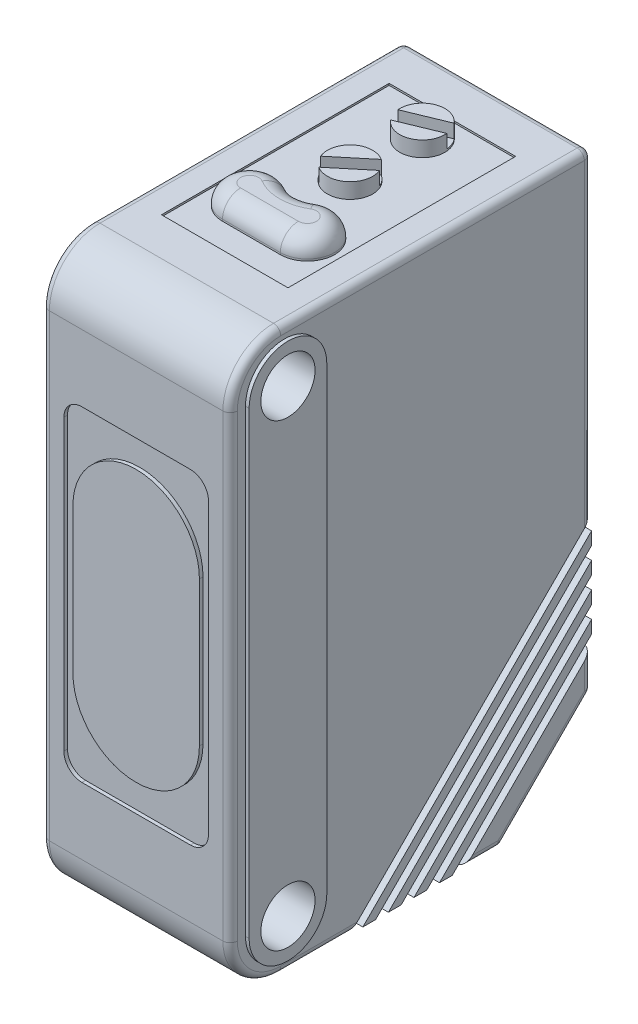
SolidWorks part; units mm, degrees
ref_plane "Plan de face" through (0, 0, 0) normal (0, 0, 1) x (1, 0, 0)
ref_plane "Plan de dessus" through (0, 0, 0) normal (0, 1, 0) x (1, 0, 0)
ref_plane "Plan de droite" through (0, 0, 0) normal (1, 0, 0) x (0, 0, -1)
sketch "Esquisse1" plane through (0, 0, 0) normal (1, 0, 0) x (0, 0, -1)
  line L0 (3, 28.2) -> (3, 2.8) construction
  line L1 (2.8, 0) -> (15, 0)
  line L2 (0, 2.8) -> (0, 28.2)
  line L3 (2.8, 31) -> (20, 31)
  line L4 (20, 5) -> (20, 31)
  line L5 (20, 5) -> (15, 0)
  circle A0 centre (3, 28.2) radius 1.5
  circle A1 centre (3, 2.8) radius 1.5
  arc A2 (2.8, 0) -> (0, 2.8) centre (2.8, 2.8) cw
  arc A3 (0, 28.2) -> (2.8, 31) centre (2.8, 28.2) cw
  point P11 (0, 0)
  dimension "D4" = 3
  dimension "D5" = 3
  dimension "D8" = 2.8
  dimension "D1" = 20
  dimension "D2" = 31
  dimension "D3" = 17
  dimension "D6" = 25.4
  dimension "D7" = 2.8
  dimension "D9" = 5
  dimension "D10" = 45
extrude "Boss.-Extru.1" add sketch "Esquisse1" along normal blind 10.4
sketch "Esquisse2" plane through (10.4, 0, 0) normal (1, 0, 0) x (0, 0, -1)
  line L0 (3, 28.2) -> (3, 2.8) construction
  line L1 (5.15, 28.2) -> (5.15, 2.8)
  line L2 (0.85, 28.2) -> (0.85, 2.8)
  arc A0 (5.15, 28.2) -> (0.85, 28.2) centre (3, 28.2) ccw
  arc A1 (0.85, 2.8) -> (5.15, 2.8) centre (3, 2.8) ccw
  circle A2 centre (3, 28.2) radius 1.5 construction
  circle A3 centre (3, 28.2) radius 1.5
  circle A4 centre (3, 2.8) radius 1.5
  point P3 (3, 15.5)
  dimension "D1" = 2.15
extrude "Boss.-Extru.3" add sketch "Esquisse2" along normal blind 0.2
sketch "Esquisse3" plane through (0, 0, 0) normal (-1, 0, 0) x (0, 0, 1)
  line L0 (-3, 28.2) -> (-3, 2.8) construction
  line L1 (-0.85, 28.2) -> (-0.85, 2.8)
  line L2 (-5.15, 28.2) -> (-5.15, 2.8)
  arc A0 (-0.85, 28.2) -> (-5.15, 28.2) centre (-3, 28.2) ccw
  arc A1 (-5.15, 2.8) -> (-0.85, 2.8) centre (-3, 2.8) ccw
  circle A2 centre (-3, 2.8) radius 1.5
  circle A3 centre (-3, 28.2) radius 1.5
  point P4 (-3, 15.5)
extrude "Boss.-Extru.4" add sketch "Esquisse3" along normal blind 0.2
sketch "Esquisse4" plane through (0, 0, 0) normal (0, 0, 1) x (1, 0, 0)
  line L0 (1.2, 15.5) -> (9.2, 15.5) construction
  line L1 (2.2, 24.5) -> (8.2, 24.5)
  line L2 (1.2, 23.5) -> (1.2, 7.5)
  line L3 (2.2, 6.5) -> (8.2, 6.5)
  line L4 (9.2, 23.5) -> (9.2, 7.5)
  line L5 (5.2, 24.5) -> (5.2, 6.5) construction
  line L6 (10.4, 0) -> (0, 0) construction
  line L7 (8.7, 19.5) -> (8.7, 11.5)
  line L8 (1.7, 19.5) -> (1.7, 11.5)
  line L9 (10.4, 28.2) -> (10.4, 2.8) construction
  arc A0 (8.7, 19.5) -> (1.7, 19.5) centre (5.2, 19.5) ccw
  arc A1 (1.7, 11.5) -> (8.7, 11.5) centre (5.2, 11.5) ccw
  arc A2 (1.2, 7.5) -> (2.2, 6.5) centre (2.2, 7.5) ccw
  arc A3 (8.2, 6.5) -> (9.2, 7.5) centre (8.2, 7.5) ccw
  arc A4 (8.2, 24.5) -> (9.2, 23.5) centre (8.2, 23.5) cw
  arc A5 (2.2, 24.5) -> (1.2, 23.5) centre (2.2, 23.5) ccw
  dimension "D2" = 4
  dimension "D5" = 8
  dimension "D7" = 1
  dimension "D1" = 18
  dimension "D3" = 4
  dimension "D4" = 15.5
  dimension "D6" = 5.2
extrude "Enlèv. mat.-Extru.1" cut sketch "Esquisse4" against normal blind 0.2
sketch "Esquisse5" plane through (10.4, 0, 0) normal (1, 0, 0) x (0, 0, -1)
  line L0 (13, 0) -> (20, 7)
  line L1 (2.8, 0) -> (15, 0) construction
  line L2 (20, 5) -> (20, 31) construction
  line L3 (20, 7) -> (20, 7.7071)
  line L4 (20, 7.7071) -> (12.2929, 0)
  line L5 (12.2929, 0) -> (13, 0)
  line L6 (11.5858, 0) -> (20, 8.4142)
  line L7 (20, 8.4142) -> (20, 9.1213)
  line L8 (20, 9.1213) -> (10.8787, 0)
  line L9 (10.8787, 0) -> (11.5858, 0)
  line L10 (20, 9.8284) -> (10.1716, 0)
  line L11 (10.1716, 0) -> (9.4645, 0)
  line L12 (9.4645, 0) -> (20, 10.5355)
  line L13 (20, 10.5355) -> (20, 9.8284)
  line L14 (20, 11.2426) -> (8.7574, 0)
  line L15 (8.7574, 0) -> (8.0503, 0)
  line L16 (8.0503, 0) -> (20, 11.9497)
  line L17 (20, 11.9497) -> (20, 11.2426)
  line L18 (7.3431, 0) -> (20, 12.6569)
  line L19 (20, 12.6569) -> (20, 13.364)
  line L20 (20, 13.364) -> (6.636, 0)
  line L21 (6.636, 0) -> (7.3431, 0)
  dimension "D1" = 2
  dimension "D2" = 45
  dimension "D3" = 0.5
  dimension "D4" = 0.5
  dimension "D5" = 0.5
  dimension "D6" = 0.5
  dimension "D7" = 0.5
  dimension "D8" = 0.5
  dimension "D9" = 0.5
  dimension "D10" = 0.5
  dimension "D11" = 0.5
extrude "Enlèv. mat.-Extru.3" cut sketch "Esquisse5" against normal blind 0.5
sketch "Esquisse7" plane through (0, 0, 0) normal (-1, 0, 0) x (0, 0, 1)
  line L0 (-20, 7) -> (-13, 0)
  line L1 (-20, 5) -> (-20, 31) construction
  line L2 (-2.8, 0) -> (-15, 0) construction
  line L3 (-13, 0) -> (-12.2929, 0)
  line L4 (-12.2929, 0) -> (-20, 7.7071)
  line L5 (-20, 7.7071) -> (-20, 7)
  line L6 (-20, 8.4142) -> (-11.5858, 0)
  line L7 (-11.5858, 0) -> (-10.8787, 0)
  line L8 (-10.8787, 0) -> (-20, 9.1213)
  line L9 (-20, 9.1213) -> (-20, 8.4142)
  line L10 (-20, 9.8284) -> (-20, 10.5355)
  line L11 (-20, 10.5355) -> (-9.4645, 0)
  line L12 (-9.4645, 0) -> (-10.1716, 0)
  line L13 (-10.1716, 0) -> (-20, 9.8284)
  line L14 (-20, 11.2426) -> (-8.7574, 0)
  line L15 (-8.7574, 0) -> (-8.0503, 0)
  line L16 (-8.0503, 0) -> (-20, 11.9497)
  line L17 (-20, 11.9497) -> (-20, 11.2426)
  line L18 (-20, 12.6569) -> (-20, 13.364)
  line L19 (-20, 13.364) -> (-6.636, 0)
  line L20 (-6.636, 0) -> (-7.3431, 0)
  line L21 (-7.3431, 0) -> (-20, 12.6569)
  dimension "D1" = 45
  dimension "D2" = 2
  dimension "D3" = 0.5
  dimension "D4" = 0.5
  dimension "D5" = 0.5
  dimension "D6" = 0.5
  dimension "D7" = 0.5
  dimension "D8" = 0.5
  dimension "D9" = 0.5
  dimension "D10" = 0.5
  dimension "D11" = 0.5
extrude "Enlèv. mat.-Extru.4" cut sketch "Esquisse7" against normal blind 0.5
fillet "Congé1" radius 0.4 21 edges at (5.2, 31, -20) (0, 22.182, -20) (10.4, 22.182, -20) (0, 31, -11.4) (10.4, 31, -11.4) (10.4, 30.1799, -0.8201) (0, 30.1799, -0.8201) (0, 0, -4.718) (0, 15.5, 0) (0, 0.8201, -0.8201) (10.4, 15.5, 0) (10.4, 0.8201, -0.8201) (10.4, 0, -4.718) (10.4, 2.5, -17.5) (10.4, 0, -14) (10.4, 6, -20) (0, 0, -14) (5.2, 0, -15) (0, 2.5, -17.5) (0, 6, -20) (5.2, 5, -20)
ref_plane "Plan1" through (0, -7.5, -7.5) normal (0, -0.7071, -0.7071) x (1, 0, 0)
sketch "Esquisse8" plane through (0, -7.5, -7.5) normal (0, -0.7071, -0.7071) x (1, 0, 0)
  line L0 (10, -14.1421) -> (0.4, -14.1421) construction
  line L1 (10, -17.512) -> (10, -10.7723) construction
  line L2 (0.4, -10.7723) -> (0.4, -17.512) construction
  circle A0 centre (5.2, -14.1421) radius 2
  dimension "D1" = 4
extrude "Boss.-Extru.5" add sketch "Esquisse8" along normal blind 3
fillet "Congé2" radius 0.4 1 edges at (5.2, 1.0858, -16.0858)
sketch "Esquisse9" plane through (0, 31, 0) normal (0, 1, 0) x (1, 0, 0)
  line L0 (5.2, 17.4987) -> (5.2, 4.9013) construction
  line L1 (1.7, 17.4987) -> (8.7, 17.4987)
  line L2 (1.7, 17.4987) -> (1.7, 4.9013)
  line L3 (1.7, 4.9013) -> (8.7, 4.9013)
  line L4 (8.7, 17.4987) -> (8.7, 4.9013)
  line L7 (1.7, 11.2) -> (8.7, 11.2) construction
  line L8 (3.6, 6.3782) -> (6.8, 6.3782)
  line L9 (0, 2.8) -> (0, 19.6) construction
  line L10 (3.6, 7.8782) -> (6.8, 7.8782) construction
  line L11 (0.4, 20) -> (10, 20) construction
  circle A0 centre (5.2, 15.8362) radius 1.25
  circle A1 centre (5.2, 11.8362) radius 1.25
  arc A2 (4.3704, 9.1652) -> (3.6, 6.3782) centre (3.6, 7.8782) ccw
  arc A3 (6.8, 6.3782) -> (6.0296, 9.1652) centre (6.8, 7.8782) ccw
  arc A4 (4.3704, 9.1652) -> (6.0296, 9.1652) centre (5.2, 10.5512) ccw
  dimension "D5" = 3
  dimension "D6" = 3
  dimension "D8" = 2.5
  dimension "D9" = 2.5
  dimension "D1" = 5.2
  dimension "D2" = 7
  dimension "D3" = 3.2
  dimension "D4" = 1.6
  dimension "D7" = 12.1218
  dimension "D10" = 4
extrude "Enlèv. mat.-Extru.5" cut sketch "Esquisse9" against normal blind 0.1
sketch "Esquisse10" plane through (0, 31, 0) normal (0, 1, 0) x (1, 0, 0)
  line L0 (3.9547, 15.7278) -> (6.1591, 16.6379)
  line L1 (4.2409, 15.0345) -> (6.4453, 15.9446)
  line L2 (4.0429, 11.3634) -> (5.8782, 12.8862)
  line L3 (4.5218, 10.7862) -> (6.3571, 12.309)
  arc A0 (6.1591, 16.6379) -> (3.9547, 15.7278) centre (5.2, 15.8362) ccw
  circle A1 centre (5.2, 15.8362) radius 1.25 construction
  arc A2 (4.5218, 10.7862) -> (6.3571, 12.309) centre (5.2, 11.8362) ccw
  circle A3 centre (5.2, 11.8362) radius 1.25 construction
  arc A4 (4.2409, 15.0345) -> (6.4453, 15.9446) centre (5.2, 15.8362) ccw
  arc A5 (5.8782, 12.8862) -> (4.0429, 11.3634) centre (5.2, 11.8362) ccw
  dimension "D1" = 0.75
  dimension "D2" = 0.375
  dimension "D3" = 0.375
  dimension "D4" = 0.75
extrude "Boss.-Extru.6" add sketch "Esquisse10" along normal blind 0.75
sketch "Esquisse12" plane through (0, 31, 0) normal (0, 1, 0) x (1, 0, 0)
  line L1 (3.6, 6.3782) -> (6.8, 6.3782)
  arc A0 (4.3704, 9.1652) -> (3.6, 6.3782) centre (3.6, 7.8782) ccw
  arc A1 (6.8, 6.3782) -> (6.0296, 9.1652) centre (6.8, 7.8782) ccw
  arc A2 (4.3704, 9.1652) -> (3.6, 6.3782) centre (3.6, 7.8782) ccw construction
  arc A3 (6.8, 6.3782) -> (6.0296, 9.1652) centre (6.8, 7.8782) ccw construction
  arc A4 (4.3704, 9.1652) -> (6.0296, 9.1652) centre (5.2, 10.5512) ccw
  arc A5 (4.3704, 9.1652) -> (6.0296, 9.1652) centre (5.2, 10.5512) ccw construction
extrude "Boss.-Extru.7" add sketch "Esquisse12" along normal blind 1
fillet "Congé3" radius 1 4 edges at (8.2458, 32, -8.2778) (5.2, 32, -6.3782) (2.1542, 32, -8.2778) (5.2, 32, -8.9359)
